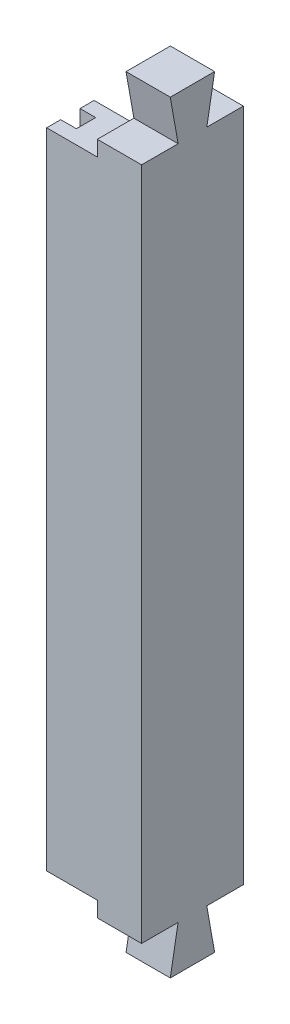
SolidWorks part; units mm, degrees
ref_plane "Front Plane" through (0, 0, 0) normal (0, 0, 1) x (1, 0, 0)
ref_plane "Top Plane" through (0, 0, 0) normal (0, 1, 0) x (1, 0, 0)
ref_plane "Right Plane" through (0, 0, 0) normal (1, 0, 0) x (0, 0, -1)
sketch "Sketch1" plane through (0, 0, 0) normal (0, 0, 1) x (1, 0, 0)
  line L1 (-10, -172.4) -> (10, -172.4)
  line L2 (-10, -172.4) -> (-10, 172.4)
  line L3 (-10, 172.4) -> (10, 172.4)
  line L4 (10, -172.4) -> (10, 172.4)
  line L5 (-10, -172.4) -> (10, 172.4) construction
  line L6 (-10, 172.4) -> (10, -172.4) construction
  point P0 (0, 0)
  dimension "D1" = 344.8
  dimension "D2" = 20
extrude "Boss-Extrude1" add sketch "Sketch1" along normal blind 46
sketch "Sketch2" plane through (-10, 0, 0) normal (-1, 0, 0) x (0, 0, 1)
  line L0 (46, 172.4) -> (0, 172.4) construction
  line L1 (46, -172.4) -> (39.65, -172.4)
  line L2 (46, -172.4) -> (46, 172.4)
  line L3 (46, 172.4) -> (39.65, 172.4)
  line L4 (39.65, -172.4) -> (39.65, 172.4)
  line L5 (46, -145.45) -> (0, -145.45)
  line L6 (46, -172.4) -> (30.9188, -172.4)
  line L7 (46, -172.4) -> (46, 172.4)
  line L8 (46, 172.4) -> (30.9188, 172.4)
  line L9 (30.9188, -172.4) -> (30.9188, 172.4)
  line L10 (46, -172.4) -> (24.5688, -172.4)
  line L11 (46, -172.4) -> (46, 172.4)
  line L12 (46, 172.4) -> (24.5688, 172.4)
  line L13 (24.5688, -172.4) -> (24.5688, 172.4)
  line L14 (0, 172.4) -> (0, -172.4) construction
  line L15 (46, 145.45) -> (0, 145.45)
  line L16 (46, -172.4) -> (0, -172.4) construction
  dimension "D1" = 6.35
  dimension "D2" = 15.0812
  dimension "D3" = 21.4312
  dimension "D4" = 26.95
  dimension "D5" = 26.95
extrude "Boss-Extrude2" add sketch "Sketch2" along normal blind 22.9 contours L2 L15 L4 L5 | L9 L15 L13 L5 region at (-10, 0, 42.825) region at (-10, 0, 27.7438)
sketch "Sketch3" plane through (-10, 0, 0) normal (-1, 0, 0) x (0, 0, 1)
  line L0 (46, -152.4) -> (29.491, -152.4)
  line L1 (0, 172.4) -> (0, -172.4) construction
  line L2 (16.509, -152.4) -> (0, -152.4)
  line L3 (29.491, -152.4) -> (16.509, -152.4)
  line L4 (16.509, -152.4) -> (12.9825, -172.4)
  line L5 (46, -172.4) -> (0, -172.4) construction
  line L6 (29.491, -152.4) -> (33.0175, -172.4)
  line L7 (0, 0) -> (24.5688, 0) construction
  line L8 (24.5688, -145.45) -> (24.5688, 145.45) construction
  line L9 (16.509, 152.4) -> (12.9825, 172.4)
  line L10 (29.491, 152.4) -> (33.0175, 172.4)
  line L11 (46, 152.4) -> (29.491, 152.4)
  line L12 (29.491, 152.4) -> (16.509, 152.4)
  line L13 (16.509, 152.4) -> (0, 152.4)
  line L14 (46, -145.45) -> (46, -172.4) construction
  line M5 (46, -172.4) -> (46, -145.45)
  line M6 (46, -145.45) -> (39.65, -145.45)
  line M8 (39.65, 145.45) -> (46, 145.45)
  line M9 (46, 145.45) -> (46, 172.4)
  line M10 (46, 172.4) -> (0, 172.4)
  line M11 (0, 172.4) -> (0, -172.4)
  line M12 (0, -172.4) -> (46, -172.4)
  line M14 (30.9188, -145.45) -> (24.5688, -145.45)
  line M16 (24.5688, 145.45) -> (30.9188, 145.45)
  dimension "D1" = 16.509
  dimension "D2" = 20.035
  dimension "D3" = 12.982
  dimension "D4" = 20
extrude "Cut-Extrude1" cut sketch "Sketch3" against normal blind 20 contours L13 L9 M10 M11 | L11 L10 M8 M9 M10 M16 | L4 L2 M11 M12 | L6 L0 M14 M12 M5 M6 region at (-10, -162.0014, 38.592) region at (-10, 162.0014, 7.408) region at (-10, -162.0014, 7.408) region at (-10, 162.0014, 38.592)
extrude "Boss-Extrude3" add sketch "Sketch2<3>" along normal blind 15.8 contours L4 L15 L9 L5 region at (-10, 0, 35.2844)
sketch "Sketch2<3>" plane through (-10, 0, 0) normal (-1, 0, 0) x (0, 0, 1) same geometry as "Sketch2"
